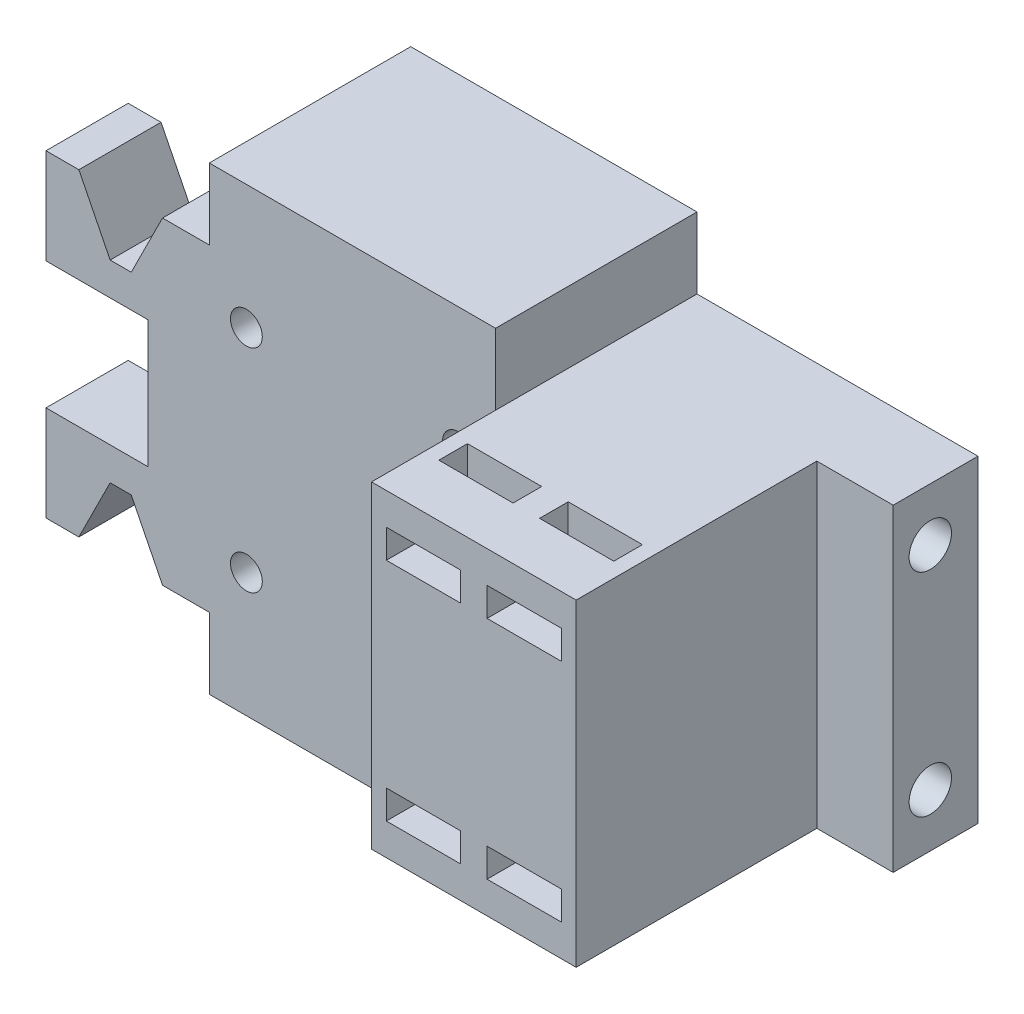
SolidWorks part; units mm, degrees
ref_plane "Front Plane" through (0, 0, 0) normal (0, 0, 1) x (1, 0, 0)
ref_plane "Top Plane" through (0, 0, 0) normal (0, 1, 0) x (1, 0, 0)
ref_plane "Right Plane" through (0, 0, 0) normal (1, 0, 0) x (0, 0, -1)
sketch "BackFace-Sketch1" plane through (0, 0, 0) normal (0, 0, 1) x (1, 0, 0)
  line L0 (0, 0) -> (0, 9)
  line L1 (0, 9) -> (9.6, 9)
  line L2 (9.6, 9) -> (9.6, 21)
  line L3 (9.6, 21) -> (0, 21)
  line L4 (0, 21) -> (0, 30)
  line L5 (0, 30) -> (3.1, 30)
  line L6 (3.1, 30) -> (6.05, 24.096)
  line L7 (6.05, 24.096) -> (8.04, 24.096)
  line L8 (8.04, 24.096) -> (10.99, 30)
  line L9 (10.99, 30) -> (15.4, 30)
  line L10 (68.9, 30) -> (68.9, 0)
  line L11 (68.9, 0) -> (42.4, 0)
  line L12 (10.99, 0) -> (8.04, 5.904)
  line L13 (8.04, 5.904) -> (6.05, 5.904)
  line L14 (6.05, 5.904) -> (3.1, 0)
  line L15 (3.1, 0) -> (0, 0)
  line L16 (15.4, 0) -> (15.4, -6.7)
  line L17 (15.4, -6.7) -> (42.4, -6.7)
  line L18 (42.4, -6.7) -> (42.4, 0)
  line L19 (15.4, 30) -> (15.4, 36.7)
  line L20 (15.4, 36.7) -> (42.4, 36.7)
  line L21 (42.4, 36.7) -> (42.4, 30)
  line L22 (42.4, 30) -> (68.9, 30)
  line L23 (15.4, 0) -> (10.99, 0)
  point P13 (4.8, 9)
  point P17 (4.575, 2.952)
  point P18 (7.045, 24.096)
  point P19 (7.045, 5.904)
  dimension "D1" = 3.1
  dimension "D2" = 9
  dimension "D4" = 6.6
  dimension "D5" = 1.99
  dimension "D7" = 30
  dimension "D8" = 9.6
  dimension "D6" = 2.95
  dimension "D9" = 27
  dimension "D10" = 43.4
  dimension "D11" = 4.41
  dimension "D3" = 26.5
  dimension "D12" = 59.3
extrude "Boss-Extrude1" add sketch "BackFace-Sketch1" along normal blind 19
sketch "EarKnotch-Sketch2" plane through (0, 0, 0) normal (0, 0, -1) x (-1, 0, 0)
  line L0 (-15.4, 30) -> (-10.99, 30) construction
  line L1 (0, 30) -> (-15.4, 30)
  line L2 (0, 30) -> (0, 0)
  line L3 (0, 0) -> (-15.4, 0)
  line L4 (-15.4, 30) -> (-15.4, 0)
  line L5 (-42.4, 0) -> (-68.9, 0) construction
  line L6 (-15.4, 36.7) -> (-15.4, 30) construction
  line L8 (0, 30) -> (0, 21) construction
extrude "EarKnotch-Cut-Extrude1" cut sketch "EarKnotch-Sketch2" against normal blind 11.25
sketch "TopHoles-Sketch3" plane through (0, 0, 0) normal (-1, 0, 0) x (0, 0, 1)
  line L0 (19, 30) -> (19, 21) construction
  line L1 (19, 30) -> (11.25, 30) construction
  line L2 (19, 0) -> (11.25, 0) construction
  circle A0 centre (14.5, 25.5) radius 2
  circle A1 centre (14.5, 4.5) radius 2
  dimension "D4" = 4
  dimension "D1" = 4.5
  dimension "D2" = 4.5
  dimension "D3" = 4.5
extrude "TopHoles-Cut-Extrude2" cut sketch "TopHoles-Sketch3" against normal blind 4
sketch "FrontHoles-Sketch1" plane through (0, 0, 0) normal (0, 0, -1) x (-1, 0, 0)
  line L0 (-68.9, 0) -> (-68.9, 30) construction
  line L1 (-68.9, 30) -> (-10.99, 30) construction
  line L2 (-42.4, 0) -> (-68.9, 0) construction
  circle A0 centre (-45.25, 25) radius 2
  circle A1 centre (-45.25, 5) radius 2
  circle A2 centre (-33.25, 25) radius 2
  circle A3 centre (-33.25, 5) radius 2
  dimension "D2" = 4
  dimension "D1" = 23.65
  dimension "D3" = 12
  dimension "D4" = 5
  dimension "D5" = 5
extrude "FrontHoles-Cut-Extrude1" cut sketch "FrontHoles-Sketch1" against normal blind 7
sketch "RearMountingHoles-Sketch2" plane through (0, 0, 19) normal (0, 0, 1) x (1, 0, 0)
  line L0 (42.4, 0) -> (68.9, 0) construction
  line L1 (15.4, 30) -> (10.99, 30) construction
  line L2 (15.4, 36.7) -> (15.4, 30) construction
  circle A0 centre (18.9, 25) radius 1.5
  circle A1 centre (18.9, 5) radius 1.5
  circle A2 centre (38.9, 25) radius 1.5
  circle A3 centre (38.9, 5) radius 1.5
  dimension "D6" = 3
  dimension "D2" = 20
  dimension "D3" = 5
  dimension "D1" = 20
  dimension "D5" = 3.5
extrude "RearMountingHoles-Cut-Extrude2" cut sketch "RearMountingHoles-Sketch2" against normal through all
sketch "RearMountingHolesBoreSketch4" plane through (0, 0, 0) normal (0, 0, -1) x (-1, 0, 0)
  circle A0 centre (-38.9, 25) radius 2.75
  circle A1 centre (-18.9, 25) radius 2.75
  circle A2 centre (-38.9, 5) radius 2.75
  circle A3 centre (-18.9, 5) radius 2.75
  dimension "D1" = 5.5
extrude "RearMountingHolesBoreCut-Extrude2" cut sketch "RearMountingHolesBoreSketch4" against normal blind 4
sketch "BlockUnderRail-Sketch1" plane through (0, 0, 19) normal (0, 0, 1) x (1, 0, 0)
  line L0 (68.9, 0) -> (68.9, 30) construction
  line L1 (42.4, 30) -> (68.9, 30)
  line L2 (42.4, 30) -> (42.4, 0)
  line L3 (42.4, 0) -> (68.9, 0)
  line L4 (68.9, 30) -> (68.9, 0)
  line L5 (68.9, 30) -> (42.4, 30) construction
  line L6 (42.4, 30) -> (42.4, 36.7) construction
extrude "BlockUnderRail-Boss-Extrude2" add sketch "BlockUnderRail-Sketch1" along normal blind 11.7
sketch "RearRibbonHoles-Sketch2" plane through (0, 0, 30.7) normal (0, 0, 1) x (1, 0, 0)
  line L0 (15.4, 36.7) -> (15.4, 30) construction
  line L1 (43.8, 27) -> (50.8, 27)
  line L2 (43.8, 27) -> (43.8, 24.3)
  line L3 (43.8, 24.3) -> (50.8, 24.3)
  line L4 (50.8, 27) -> (50.8, 24.3)
  line L5 (53.3, 27) -> (60.3, 27)
  line L6 (53.3, 27) -> (53.3, 24.3)
  line L7 (53.3, 24.3) -> (60.3, 24.3)
  line L8 (60.3, 27) -> (60.3, 24.3)
  line L9 (43.8, 5.7) -> (50.8, 5.7)
  line L10 (43.8, 5.7) -> (43.8, 3)
  line L11 (43.8, 3) -> (50.8, 3)
  line L12 (50.8, 5.7) -> (50.8, 3)
  line L13 (53.3, 5.7) -> (60.3, 5.7)
  line L14 (53.3, 5.7) -> (53.3, 3)
  line L15 (53.3, 3) -> (60.3, 3)
  line L16 (60.3, 5.7) -> (60.3, 3)
  line L20 (42.4, 0) -> (68.9, 0) construction
  line L21 (68.9, 30) -> (42.4, 30) construction
  dimension "D3" = 2.7
  dimension "D4" = 7
  dimension "D5" = 2.5
  dimension "D2" = 3
  dimension "D1" = 3
  dimension "D6" = 28.4
extrude "RearRibbonHoles-Cut-Extrude1" cut sketch "RearRibbonHoles-Sketch2" against normal blind 7.65
sketch "LeftRibbonHoles-Sketch3" plane through (0, 0, 0) normal (0, -1, 0) x (1, 0, 0)
  line L0 (43.8, 23.05) -> (50.8, 23.05) construction
  line L1 (43.8, 25.75) -> (50.8, 25.75)
  line L2 (43.8, 25.75) -> (43.8, 23.05)
  line L3 (43.8, 23.05) -> (50.8, 23.05)
  line L4 (50.8, 25.75) -> (50.8, 23.05)
  line L5 (53.3, 25.75) -> (60.3, 25.75)
  line L6 (53.3, 25.75) -> (53.3, 23.05)
  line L7 (53.3, 23.05) -> (60.3, 23.05)
  line L8 (60.3, 25.75) -> (60.3, 23.05)
  line L9 (43.8, 23.05) -> (43.8, 30.7) construction
  line L10 (50.8, 23.05) -> (50.8, 30.7) construction
  line L11 (53.3, 23.05) -> (53.3, 30.7) construction
  line L12 (60.3, 23.05) -> (60.3, 30.7) construction
  dimension "D1" = 2.7
sketch "RightRibbonHoles-Sketch4" plane through (0, 30, 0) normal (0, 1, 0) x (1, 0, 0)
  line L0 (60.3, -23.05) -> (53.3, -23.05) construction
  line L9 (50.8, -23.05) -> (43.8, -23.05) construction
  line L10 (43.8, -23.05) -> (43.8, -30.7) construction
  line L11 (53.3, -23.05) -> (53.3, -30.7) construction
  line L13 (60.3, -23.05) -> (60.3, -30.7) construction
  line L14 (43.8, -23.05) -> (50.8, -23.05)
  line L15 (43.8, -23.05) -> (43.8, -25.75)
  line L16 (43.8, -25.75) -> (50.8, -25.75)
  line L17 (50.8, -23.05) -> (50.8, -25.75)
  line L18 (53.3, -23.05) -> (60.3, -23.05)
  line L19 (53.3, -23.05) -> (53.3, -25.75)
  line L20 (53.3, -25.75) -> (60.3, -25.75)
  line L21 (60.3, -23.05) -> (60.3, -25.75)
  line L22 (50.8, -23.05) -> (50.8, -30.7) construction
  line L23 (50.8, -23.05) -> (43.8, -23.05) construction
  line L26 (55.51, -26.7) -> (33.1572, -26.7) construction
  line L27 (50.99, -27.35) -> (33.1572, -27.35) construction
  line L28 (42.4, -19) -> (15.4, -19) construction
  dimension "D1" = 2.7
  dimension "D2" = 8.35
extrude "RightRibbonHoles-Cut-Extrude2" cut sketch "RightRibbonHoles-Sketch4" against normal blind 5.7
extrude "LeftRibbonHoles-Cut-Extrude2" cut sketch "LeftRibbonHoles-Sketch3" against normal blind 5.7
sketch "BottomClampMountingHolesSketch3" plane through (68.9, 0, 0) normal (1, 0, 0) x (0, 0, -1)
  line L0 (-19, 30) -> (0, 30) construction
  line L1 (-19, 0) -> (0, 0) construction
  line L4 (0, 0) -> (0, 30) construction
  circle A0 centre (-4.5, 25) radius 2
  circle A1 centre (-4.5, 5) radius 2
  dimension "D3" = 5
  dimension "D1" = 4
  dimension "D2" = 5
  dimension "D4" = 4.5
extrude "BottomClampMountHolesCut-Extrude1" cut sketch "BottomClampMountingHolesSketch3" against normal blind 4.1
fillet "RibbonHoleFillet1" radius 2.7 1 edges at (56.8, 5.7, 23.05)
fillet "RibbonHoleFillet2" radius 2.7 1 edges at (47.3, 5.7, 23.05)
fillet "RibbonHoleFillet3" radius 2.7 1 edges at (56.8, 24.3, 23.05)
fillet "RibbonHoleFillet4" radius 2.7 1 edges at (47.3, 24.3, 23.05)
sketch "ExcessEndSketch1" plane through (0, 0, 30.7) normal (0, 0, 1) x (1, 0, 0)
  line L0 (42.4, 0) -> (68.9, 0) construction
  line L1 (68.9, 30) -> (61.7, 30)
  line L2 (68.9, 30) -> (68.9, 0)
  line L3 (68.9, 0) -> (61.7, 0)
  line L4 (61.7, 30) -> (61.7, 0)
  line L5 (60.3, 27) -> (60.3, 24.3) construction
  dimension "D1" = 1.4
extrude "ExcessEndCut-Extrude1" cut sketch "ExcessEndSketch1" against normal blind 22.7
equation "\"CarrierWidth\"= \"LinearGBWidthWithBumpers\" - 2mm"
equation "\"LinearGBWidth\"= 27mm'Spec"
equation "\"D10@BackFace-Sketch1\"=\"CarrierWidth\""
equation "\"LinearGBWidthWithBumpers\"= 45.4mm"
equation "\"LinearGBMountHolesXDistance\"= 20mm'Spec"
equation "\"LinearGBMountHolesYDistance\"= 20mm'Spec"
equation "\"D1@RearMountingHoles-Sketch2\"=\"LinearGBMountHolesXDistance\""
equation "\"D2@RearMountingHoles-Sketch2\"=\"LinearGBMountHolesYDistance\""
equation "\"D5@RearMountingHoles-Sketch2\"= ( \"LinearGBWidth\" - \"LinearGBMountHolesYDistance\" ) / 2"
equation "\"CarrierRibbonHoleWidth\"= 7mm"
equation "\"CarrierRibbonHoleHeight\"= 2.7mm"
equation "\"CarrierRibbonHoleDistance\"= 2.5mm'Equals 2.5. Must equal distance created by GABRiserBossOffset"
equation "\"CarrierRibbonHoleOffsetFromSide\"= 3.0mm"
equation "\"CarrierDepth\"= 19mm"
equation "\"D1@Boss-Extrude1\"=\"CarrierDepth\""
equation "\"D3@RearRibbonHoles-Sketch2\" = \"CarrierRibbonHoleHeight\""
equation "\"D4@RearRibbonHoles-Sketch2\" = \"CarrierRibbonHoleWidth\""
equation "\"D5@RearRibbonHoles-Sketch2\" = \"CarrierRibbonHoleDistance\""
equation "\"D9@BackFace-Sketch1\"=\"LinearGBWidth\""
equation "\"D2@RearRibbonHoles-Sketch2\"=\"CarrierRibbonHoleOffsetFromSide\""
equation "\"D1@RearRibbonHoles-Sketch2\"=\"CarrierRibbonHoleOffsetFromSide\""
equation "\"D1@RightRibbonHoles-Cut-Extrude2\" = \"CarrierRibbonHoleOffsetFromSide\" + \"CarrierRibbonHoleHeight\""
equation "\"LinearRailHeight\"= 8mm'Spec"
equation "\"LinearGBDepth\"= 10mm'Spec"
equation "\"D1@BlockUnderRail-Boss-Extrude2\"=\"MiddleOfGBAndLinearRail\" +  \"CarrierRibbonHoleHeight\""
equation "\"D1@LeftRibbonHoles-Cut-Extrude2\" = \"CarrierRibbonHoleOffsetFromSide\" + \"CarrierRibbonHoleHeight\""
equation "\"D1@RightRibbonHoles-Sketch4\"=\"CarrierRibbonHoleHeight\""
equation "\"D1@RearRibbonHoles-Cut-Extrude1\"=\"MiddleOfGBAndLinearRail\" - \"CarrierRibbonHoleHeight\"/2mm"
equation "\"D1@LeftRibbonHoles-Sketch3\"=\"CarrierRibbonHoleHeight\""
equation "\"MiddleOfGBAndLinearRail\"= \"LinearGBDepth\" / 2 + \"LinearRailHeight\" / 2"
equation "\"CarrierUpperBodyLength\"= \"CarrierBodyLength\" - \"LinearGBWidth\" - \"CarrierLowerBodyLength\""
equation "\"CarrierLowerBodyLength\"= \"CarrierRibbonHoleWidth\" * 2 + \"CarrierRibbonHoleDistance\" + 5mm * 2"
equation "\"D3@BackFace-Sketch1\"=\"CarrierLowerBodyLength\""
equation "\"D11@BackFace-Sketch1\"=\"CarrierUpperBodyLength\""
equation "\"CarrierBodyLength\"= 59.3mm - 1.39mm'From the 100 1.39 accounts for the little slant"
equation "\"M3HeatInsertHoleDiamter\"=4"
equation "\"D1@BottomClampMountingHolesSketch3\"=\"M3HeatInsertHoleDiamter\""
equation "\"M3HeatInsertHoleDepth\"= 4.1mm'Spec"
equation "\"D1@BottomClampMountHolesCut-Extrude1\"=\"M3HeatInsertHoleDepth\""
equation "\"D1@RibbonHoleFillet1\" = \"CarrierRibbonHoleHeight\""
equation "\"D1@RibbonHoleFillet2\"=\"CarrierRibbonHoleHeight\""
equation "\"D1@RibbonHoleFillet3\"=\"CarrierRibbonHoleHeight\""
equation "\"D1@RibbonHoleFillet4\"=\"CarrierRibbonHoleHeight\""
equation "\"M3ScrewHoleDiameter\"= 3mm"
equation "\"M3ButtonHeadDiameter\"= 5.5mm"
equation "\"D6@RearMountingHoles-Sketch2\"=\"M3ScrewHoleDiameter\""
equation "\"D1@RearMountingHolesBoreSketch4\"=\"M3ButtonHeadDiameter\""
equation "\"D4@TopHoles-Sketch3\"=\"M3HeatInsertHoleDiamter\""
equation "\"D2@FrontHoles-Sketch1\"=\"M3HeatInsertHoleDiamter\""
